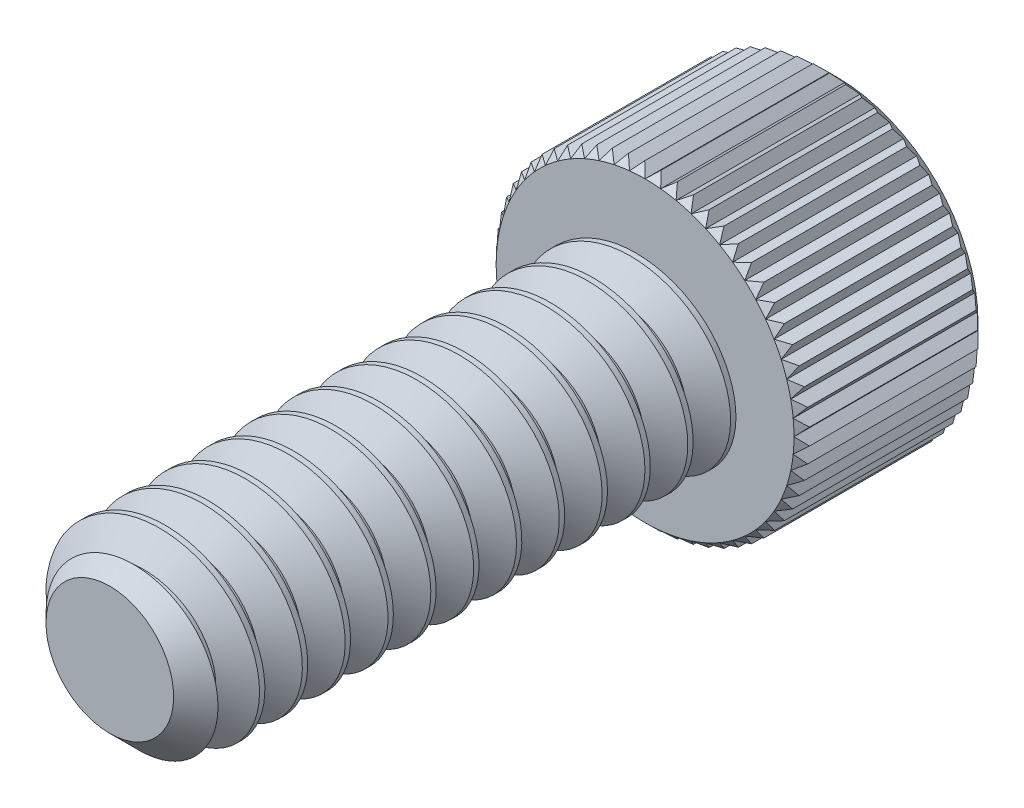
SolidWorks part; units mm, degrees
note: '?' marks a value the reader was unsure of.
ref_plane "Front Plane" through (0, 0, 0) normal (0, 0, 1) x (1, 0, 0)
ref_plane "Top Plane" through (0, 0, 0) normal (0, 1, 0) x (1, 0, 0)
ref_plane "Right Plane" through (0, 0, 0) normal (1, 0, 0) x (0, 0, -1)
sketch "Sketch0" plane through (0, 0, 0) normal (1, 0, 0) x (0, 0, -1)
  line L0 (0, 0) -> (7.9375, 0) construction
  point P2 (10.7823, 0)
  point P4 (0, 0)
  dimension "D1" = 7.9375
  dimension "D2" = 2.8448
  dimension "Min Thread" = 0
sketch "Sketch1" plane through (0, 0, 0) normal (0, 0, 1) x (1, 0, 0)
  circle A0 centre (0, 0) radius 1.4224
  dimension "OD" = 2.8448
extrude "Extrude1" add sketch "Sketch1" against normal blind 7.9375
sketch "Sketch2" plane through (0, 0, 0) normal (0, 0, 1) x (1, 0, 0)
  circle A0 centre (0, 0) radius 1.4224 construction
  circle A1 centre (0, 0) radius 1.4224
curve "Helix/Spiral1" pitch 0.635 height 8.5725 radius 1.4224 centre (0, 0, 0) axis (0, 0, -1) start towards (0, 1, 0) parameters "pitch"=0.635
chamfer "Chamfer3" distance 0.4763 angle 45 1 edges at (1.4224, 0, 0)
sketch "Sketch3" plane through (0, 0, 0) normal (1, 0, 0) x (0, 0, -1)
  line L0 (-0.5556, 1.4224) -> (-0.3175, 1.01)
  line L1 (-0.3175, 1.01) -> (-0.2381, 1.01)
  line L2 (-0.2381, 1.01) -> (0, 1.4224)
  line L3 (-0.5556, 1.4224) -> (0, 1.4224)
  line L4 (-0.2778, 1.4224) -> (-0.2778, 1.01) construction
  line L5 (-0.4366, 1.2162) -> (-0.1191, 1.2162) construction
  line L6 (0, 1.4224) -> (0, -1.4224) construction
  dimension "D1" = 0.0794
  dimension "D2" = 0.3175
  dimension "D3" = 60
sweep "Cut-Sweep1" cut profiles "Sketch3" path "Helix/Spiral1" align with end faces yes
sketch "Sketch5" plane through (0, 0, 0) normal (1, 0, 0) x (0, 0, -1)
  line L0 (7.9375, -1.0149) -> (7.9375, 1.0232) construction
  line L1 (7.9375, 1.4224) -> (0, 1.4224)
  line L2 (7.9375, 1.4224) -> (7.9375, 0)
  line L3 (7.9375, 0) -> (-0.5177, 0)
  line L4 (0, 0) -> (7.9375, 0) construction
  line L5 (0, 1.4224) -> (-0.5177, 0)
  line L6 (0, 0) -> (10.4775, 0) construction
  dimension "D1" = 70
  dimension "D3" = 2.54
revolve "partially thread" [suppressed] add sketch "Sketch5" angle 360 about L6
sketch "Sketch6" plane through (0, 0, -7.9375) normal (0, 0, -1) x (-1, 0, 0)
  circle A0 centre (0, 0) radius 2.3241
  dimension "head dia" = 4.6482
extrude "Extrude2" add sketch "Sketch6" along normal blind 2.8448
sketch "Sketch7" plane through (0, 0, -10.7823) normal (0, 0, -1) x (-1, 0, 0)
  line L1 (0, 1.3748) -> (-1.1906, 0.6874)
  line L2 (-1.1906, 0.6874) -> (-1.1906, -0.6874)
  line L3 (-1.1906, -0.6874) -> (0, -1.3748)
  line L4 (0, -1.3748) -> (1.1906, -0.6874)
  line L5 (1.1906, -0.6874) -> (1.1906, 0.6874)
  line L6 (1.1906, 0.6874) -> (0, 1.3748)
  circle A0 centre (0, 0) radius 1.1906 construction
  dimension "hex dia" = 2.3813
extrude "Cut-Extrude1" cut sketch "Sketch7" against normal blind 1.7859
sketch "Sketch8" plane through (0, 0, -10.7823) normal (0, 0, -1) x (-1, 0, 0)
  circle A0 centre (0, 0) radius 1.3748
extrude "Cut-Extrude2" cut sketch "Sketch8" against normal through all draft 45
chamfer "Chamfer1" distance 0.2324 angle 45 1 edges at (-2.3241, 0, -10.7823)
chamfer "Chamfer2" distance 0.1162 angle 45 1 edges at (-2.3241, 0, -7.9375)
sketch "Sketch9" plane through (0, 0, 0) normal (1, 0, 0) x (0, 0, -1)
  line L0 (0, 1.4224) -> (0, -1.4224) construction
  line L1 (1.5875, 1.4224) -> (1.5875, -1.4224) construction
  line L2 (10.7823, 2.3241) -> (10.7823, -2.3241) construction
  line L3 (7.9375, 2.3241) -> (7.9375, -2.3241) construction
  line L4 (7.9375, 2.2079) -> (7.9375, -2.2079) construction
  line L5 (10.7823, -2.0917) -> (10.7823, 2.0917) construction
  line L6 (7.9375, -2.3241) -> (7.9375, 2.3241) construction
  line L7 (0, 0.9461) -> (0, -0.9461) construction
  line L8 (-0.5556, 1.4224) -> (0, 1.4224) construction
  line L9 (1.5875, 0) -> (0, 0) construction
  dimension "D1" = 1.5875
sketch "Sketch10" plane through (0, 0, -7.9375) normal (0, 0, 1) x (1, 0, 0)
  line L0 (-0.2501, 2.4403) -> (0, 2.2079)
  line L1 (0, 2.2079) -> (0.2501, 2.4403)
  line L2 (0, 2.2079) -> (0, 2.4403) construction
  line L3 (-0.2501, 2.4403) -> (0.2501, 2.4403)
  line L4 (0, -2.553) -> (0, 2.553) construction
  line L5 (0, 0) -> (0.1216, 2.3209) construction
  line L6 (-0.1216, 2.3209) -> (0, 0) construction
  circle A2 centre (0, 0) radius 2.3241 construction
  circle A5 centre (0, 0) radius 2.2079 construction
  dimension "D1" = 6
  dimension "D2" = 0.2324
extrude "Cut-Extrude3" cut sketch "Sketch10" against normal through all
pattern_circular "CirPattern1" count 60 over 360 about axis through (0, 0, 0) along (0, 0, 1) of "Cut-Extrude3"
ref_plane "Contact Plane 1" through (0, 0, -7.9375) normal (0, 0, 1) x (1, 0, 0)
ref_axis "Center Axis 1" through (0, 0, 0.8878) along (0, 0, -1)?
equation "\"D3@Helix/Spiral1\" = \"screw length@Extrude1\"+\"pitch@Helix/Spiral1\""
equation "\"D1@Sketch3\" = \"pitch@Helix/Spiral1\"*.125"
equation "\"D2@Sketch3\" = \"pitch@Helix/Spiral1\"*.5"
equation "\"D1@Cut-Extrude1\" = \"hex dia@Sketch7\"*.75"
equation "\"D1@Chamfer1\" = \"head dia@Sketch6\"*.05"
equation "\"D1@Sketch9\" = \"pitch@Helix/Spiral1\"*2.50"
equation "\"D1@Chamfer2\" = \"D1@Chamfer1\"/2"
equation "\"D1@Chamfer3\" = \"pitch@Helix/Spiral1\"*.750"
equation "\"D1@Sketch0\" = \"screw length@Extrude1\""
equation "\"D2@Sketch0\" = \"head depth@Extrude2\""
equation "\"D2@Sketch10\"=\"D1@Chamfer1\""
equation "\"D1@CirPattern1\"=\"D3@CirPattern1\"/\"D1@Sketch10\""
